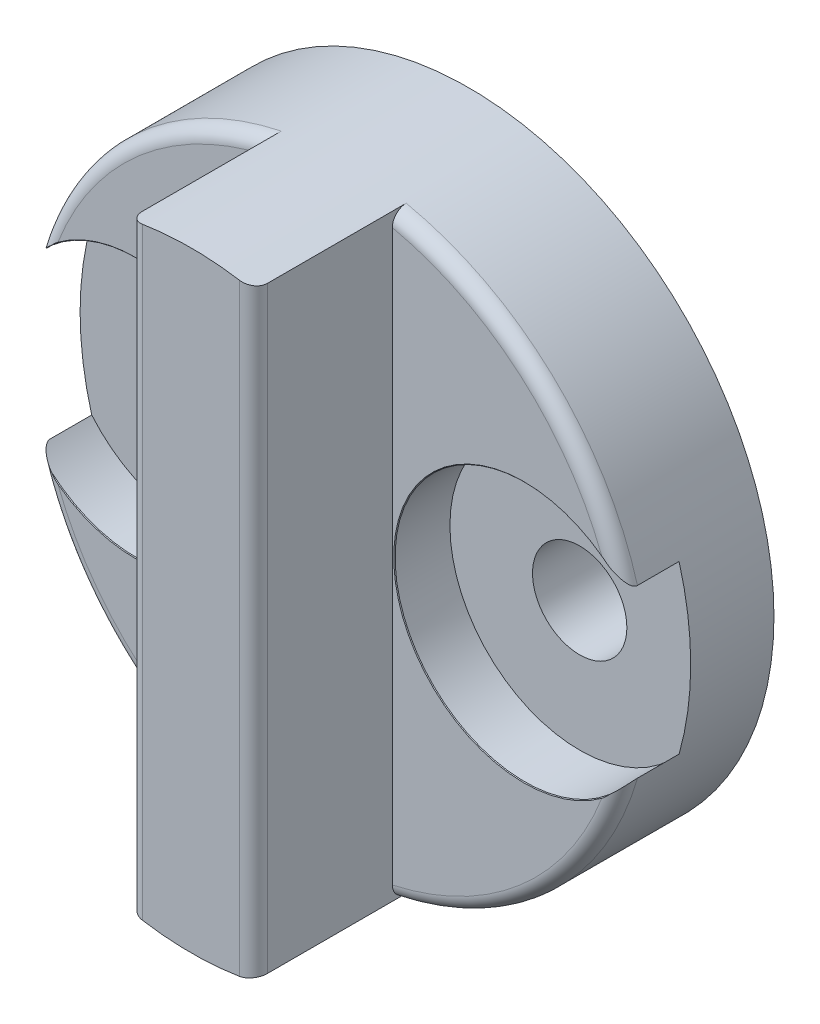
SolidWorks part; units mm, degrees
material "ABS PC"
ref_plane "Plan de face" through (0, 0, 0) normal (0, 0, 1) x (1, 0, 0)
ref_plane "Plan de dessus" through (0, 0, 0) normal (0, 1, 0) x (1, 0, 0)
ref_plane "Plan de droite" through (0, 0, 0) normal (1, 0, 0) x (0, 0, -1)
sketch "Esquisse1" plane through (0, 0, 0) normal (0, 0, 1) x (1, 0, 0)
  circle A0 centre (0, 0) radius 11
  dimension "D1" = 22
extrude "Boss.-Extru.1" add sketch "Esquisse1" along normal blind 5
sketch "Esquisse2" plane through (0, 0, 5) normal (0, 0, 1) x (1, 0, 0)
  line L0 (0, 5.7045) -> (0, -6.8994) construction
  line L2 (-2.25, 10.7674) -> (-2.25, -10.7674)
  line L4 (2.25, 10.7674) -> (2.25, -10.7674)
  circle A0 centre (0, 0) radius 11 construction
  arc A1 (-2.25, -10.7674) -> (2.25, -10.7674) centre (0, 0) ccw
  arc A2 (2.25, 10.7674) -> (-2.25, 10.7674) centre (0, 0) ccw
  dimension "D1" = 4.5
extrude "Boss.-Extru.2" add sketch "Esquisse2" along normal blind 5
fillet "Congé1" radius 0.5 2 edges
fillet "Congé2" radius 0.5 2 edges at (-2.25, 0, 10) (2.25, 0, 10)
sketch "Esquisse3" plane through (0, 0, 5) normal (0, 0, 1) x (1, 0, 0)
  line L0 (-10.5, 0) -> (10.5, 0) construction
  line L1 (0, 8.9439) -> (0, -6.8163) construction
  circle A0 centre (-7, 0) radius 1.5
  circle A1 centre (7, 0) radius 1.5
  arc A2 (-2.25, 10.2561) -> (-2.25, -10.2561) centre (0, 0) ccw construction
  arc A3 (2.25, -10.2561) -> (2.25, 10.2561) centre (0, 0) ccw construction
  dimension "D1" = 3
  dimension "D2" = 14
hole_wizard "Chambrage pour vis à tête hexagonale M31" positions "Esquisse3D1" profile "Esquisse4" counterbore size "M3" standard "Iso" end condition through all
sketch3d "Esquisse3D1"
  point P0 (-7, 0, 5)
  point P3 (7, 0, 5)
sketch "Esquisse4" plane through (-7, 0, 5) normal (1, 0, 0) x (0, -1, 0)
  line L0 (0, 0) -> (0, 5)
  line L1 (0, 5) -> (1.7, 5)
  line L3 (1.7, 5) -> (1.7, 2)
  line L4 (4.6755, 2) -> (1.7, 2)
  line L5 (4.6755, 2) -> (4.6755, 0.025)
  line L6 (4.6755, 0.025) -> (4.7005, 0)
  line L7 (4.7005, 0) -> (0, 0)
  line L8 (-4.6755, 0.025) -> (-4.7005, 0) construction
  line L11 (0, -6.35) -> (0, 107.95) construction
  dimension "Diamètre du perçage jusqu'au prochain" = 3.4
  dimension "Profondeur du perçage jusqu'au prochain" = 5
  dimension "Diamètre du chambrage" = 9.351
  dimension "Profondeur du chambrage" = 2
  dimension "Diamètre du fraisage entrant" = 9.401
  dimension "Angle du fraisage entrant" = 90
